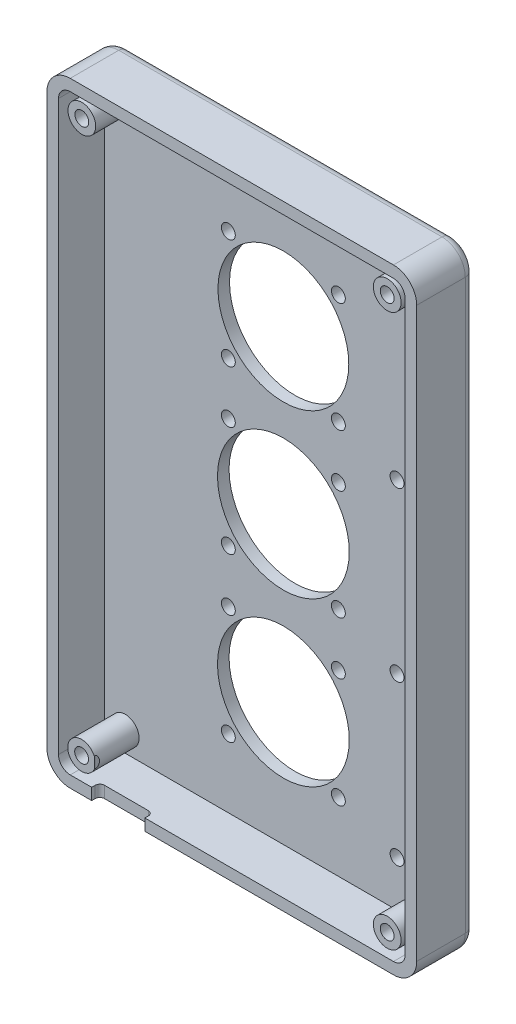
SolidWorks part; units mm, degrees
material "Plastique personnalisé"
ref_plane "Plan de face" through (0, 0, 0) normal (0, 0, 1) x (1, 0, 0)
ref_plane "Plan de dessus" through (0, 0, 0) normal (0, 1, 0) x (1, 0, 0)
ref_plane "Plan de droite" through (0, 0, 0) normal (1, 0, 0) x (0, 0, -1)
sketch "Esquisse1" plane through (0, 0, 0) normal (0, 0, 1) x (1, 0, 0)
  line L1 (-34.96, -64) -> (34.96, -64)
  line L2 (-37.5, -61.46) -> (-37.5, 61.46)
  line L3 (-34.96, 64) -> (34.96, 64)
  line L4 (37.5, -61.46) -> (37.5, 61.46)
  line L5 (-37.5, -64) -> (37.5, 64) construction
  line L6 (-37.5, 64) -> (37.5, -64) construction
  arc A0 (34.96, -64) -> (37.5, -61.46) centre (34.96, -61.46) ccw
  arc A1 (-34.96, -64) -> (-37.5, -61.46) centre (-34.96, -61.46) cw
  arc A2 (-37.5, 61.46) -> (-34.96, 64) centre (-34.96, 61.46) cw
  arc A3 (34.96, 64) -> (37.5, 61.46) centre (34.96, 61.46) cw
  point P0 (0, 0)
  dimension "D3" = 2.54
  dimension "D1" = 128
  dimension "D2" = 75
extrude "Boss.-Extru.1" add sketch "Esquisse1" along normal blind 10
shell "Coque1" thickness 2.5 removed face at (0, 0, 10) outward yes
fillet "Congé1" radius 2 8 edges at (40, 0, -2.5) (38.5238, -65.0238, -2.5) (0, -66.5, -2.5) (-38.5238, -65.0238, -2.5) (-40, 0, -2.5) (-38.5238, 65.0238, -2.5) (0, 66.5, -2.5) (38.5238, 65.0238, -2.5)
sketch "Esquisse3" plane through (0, 0, 0) normal (0, 0, 1) x (1, 0, 0)
  circle A0 centre (-33.02, 59.69) radius 1.5
  circle A1 centre (-33.02, 59.69) radius 3
  circle A2 centre (33.0465, 59.69) radius 1.5
  circle A3 centre (33.0465, 59.69) radius 3
  circle A4 centre (-33.06, -59.69) radius 3
  circle A5 centre (-33.06, -59.69) radius 1.5
  circle A6 centre (33.0465, -59.759) radius 3
  circle A7 centre (33.0465, -59.759) radius 1.5
  dimension "D1" = 3
  dimension "D2" = 3
extrude "Boss.-Extru.2" add sketch "Esquisse3" along normal up to surface (9.43 mm away)
sketch "Esquisse4" plane through (0, 0, 10) normal (0, 0, 1) x (1, 0, 0)
  line L0 (-24.5364, -63.3046) -> (-24.5364, -64) construction
  line L1 (-34.96, -64) -> (34.96, -64) construction
  line L2 (-24.5364, -64) -> (-24.5364, -64.0598) construction
  line L3 (-24.5364, -64.0598) -> (-24.5364, -66.5) construction
  line L4 (-34.96, -66.5) -> (34.96, -66.5) construction
  line L6 (-29.52, -66.5598) -> (-19.5528, -66.5598)
  line L7 (-29.52, -66.5598) -> (-29.52, -64)
  line L8 (-29.52, -64) -> (-19.5528, -64)
  line L9 (-19.5528, -66.5598) -> (-19.5528, -64)
  line L10 (-29.52, -66.5598) -> (-19.5528, -64) construction
  line L11 (-29.52, -64) -> (-19.5528, -66.5598) construction
  point P5 (-24.5364, -65.2799)
extrude "Enlèv. mat.-Extru.2" cut sketch "Esquisse4" against normal blind 1
fillet "Congé4" radius 1 2 edges at (-19.5528, -65.25, 9) (-29.52, -65.25, 9)
sketch "Esquisse5" plane through (0, 0, -2.5) normal (0, 0, -1) x (-1, 0, 0)
  circle A0 centre (-13.049, 44.9581) radius 1.5
  circle A1 centre (10.751, 44.9581) radius 1.5
  circle A2 centre (10.751, 21.1581) radius 1.5
  circle A3 centre (-13.049, 21.1581) radius 1.5
  circle A4 centre (-13.049, 9.7959) radius 1.5
  circle A5 centre (10.751, 9.8247) radius 1.5
  circle A6 centre (10.751, -13.9753) radius 1.5
  circle A7 centre (-13.049, -13.9753) radius 1.5
  circle A8 centre (-13.049, -25.3963) radius 1.5
  circle A9 centre (10.751, -25.3963) radius 1.5
  circle A10 centre (10.751, -49.1963) radius 1.5
  circle A11 centre (-13.049, -49.1963) radius 1.5
  circle A12 centre (-1.149, -37.2963) radius 14.25
  circle A13 centre (-1.149, -2.0753) radius 14.25
  circle A14 centre (-1.149, 33.0581) radius 14.15
  dimension "D1" = 3
  dimension "D2" = 3
  dimension "D3" = 3
  dimension "D4" = 3
  dimension "D5" = 3
  dimension "D6" = 3
  dimension "D7" = 3
  dimension "D8" = 3
  dimension "D9" = 3
  dimension "D10" = 3
  dimension "D11" = 3
  dimension "D12" = 3
extrude "Enlèv. mat.-Extru.3" cut sketch "Esquisse5" against normal blind 10
sketch "Esquisse6" plane through (0, 0, 0) normal (0, 0, 1) x (1, 0, 0)
  circle A0 centre (25.7401, 16.6531) radius 1.5
  circle A1 centre (25.7401, -19.683) radius 1.5
  circle A2 centre (25.7401, -54.1208) radius 1.5
extrude "Enlèv. mat.-Extru.4" cut sketch "Esquisse6" against normal blind 10
sketch "Esquisse7" plane through (0, -66.5, 0) normal (0, -1, 0) x (1, 0, 0)
  line L0 (-29.52, 10) -> (-19.5528, 10) construction
  line L1 (-24.5668, 10) -> (-24.5668, 8.25) construction
  line L3 (-29.3168, 8.2408) -> (-19.8168, 8.2408)
  line L4 (-30.3168, 9.2408) -> (-30.3168, 10.0092)
  line L5 (-30.3168, 10.0092) -> (-18.8168, 10.0092)
  line L6 (-18.8168, 9.2408) -> (-18.8168, 10.0092)
  line L7 (-30.3168, 8.2408) -> (-18.8168, 10.0092) construction
  line L8 (-30.3168, 10.0092) -> (-18.8168, 8.2408) construction
  arc A0 (-29.3168, 8.2408) -> (-30.3168, 9.2408) centre (-29.3168, 9.2408) cw
  arc A1 (-18.8168, 9.2408) -> (-19.8168, 8.2408) centre (-19.8168, 9.2408) cw
  point P6 (-24.5668, 9.125)
  dimension "D2" = 1
  dimension "D1" = 1.75
  dimension "D3" = 11.5
extrude "Enlèv. mat.-Extru.5" cut sketch "Esquisse7" against normal blind 10
